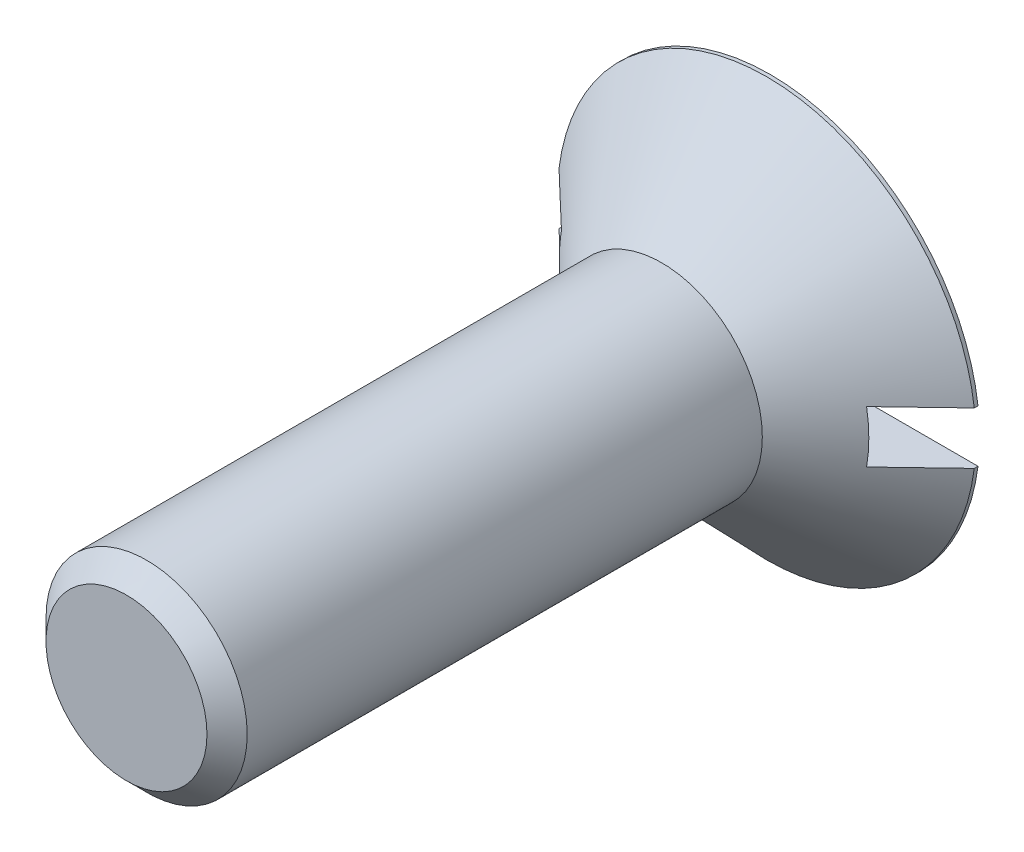
SolidWorks part; units mm, degrees
material "Acier allié"
ref_plane "Plan1" through (0, 0, 0) normal (0, 0, 1) x (1, 0, 0)
ref_plane "Plan2" through (0, 0, 0) normal (0, 1, 0) x (1, 0, 0)
ref_plane "Plan3" through (0, 0, 0) normal (1, 0, 0) x (0, 0, -1)
ref_axis "Z Axis" through (0, 0, -50) along (0, 0, 1)
sketch "Esquisse1" plane through (0, 0, 0) normal (0, 1, 0) x (1, 0, 0)
  line L0 (2.5, 0) -> (5.2, 2.6074)
  line L1 (0, 0) -> (2.5, 0)
  line L2 (0, 0) -> (0, 2.7)
  line L3 (0, 2.7) -> (5.2, 2.7)
  line L5 (5.2, 2.6074) -> (5.2, 2.7)
  line L6 (0, 0) -> (0, 2.7) construction
  dimension "D3" = 5.2
  dimension "D1" = 2.5
  dimension "D2" = 46
  dimension "D4" = 2.7
revolve "Base-Révolution" add sketch "Esquisse1" angle 360 about L6 reverse direction yes
sketch "Esquisse2" plane through (0, 0, -2.7) normal (0, 0, 1) x (1, 0, 0)
  line L1 (-5.2, 0.65) -> (5.2, 0.65)
  line L2 (-5.2, 0.65) -> (-5.2, -0.65)
  line L3 (-5.2, -0.65) -> (5.2, -0.65)
  line L4 (5.2, 0.65) -> (5.2, -0.65)
  circle A1 centre (0, 0) radius 5.2 construction
extrude "fente1" cut sketch "Esquisse2" along normal blind 1.4
sketch "Esquisse3" plane through (0, 0, 0) normal (0, 1, 0) x (1, 0, 0)
  line L1 (0, 0) -> (0, -13.3) construction
  line L2 (0, 0) -> (2.5, 0)
  line L3 (0, 0) -> (0, -13.3)
  line L4 (0, -13.3) -> (2.5, -13.3)
  line L6 (2.5, 0) -> (2.5, -13.3)
  dimension "D1" = 13.3
  dimension "D2" = 2.5
revolve "Boss.-Révol.1" add sketch "Esquisse3"
cosmetic thread "Représentation de filetage1" [suppressed]
chamfer "Chanfrein1" distance 0.5 angle 45 1 edges at (2.5, 0, 13.3)
sketch "Esquisse4" plane through (0, 0, 0) normal (0, 1, 0) x (1, 0, 0)
  line L0 (2.012, -13.3488) -> (2.012, -13.2512)
  line L2 (2.012, -13.2512) -> (2.5488, -12.9413)
  line L3 (2.012, -13.3488) -> (2.5488, -13.6587)
  line L4 (2.5488, -12.9413) -> (2.5488, -13.6587)
  line L6 (-2.5, -13.3) -> (2.5, -13.3) construction
  line L7 (2.5, -13.3) -> (2.5, 0) construction
  point P4 (2.5, -13.3)
  dimension "D2" = 0.0488
  dimension "D3" = 0.0488
  dimension "D4" = 0.5368
  dimension "D5" = 60
  dimension "D1" = 0.488
  dimension "D6" = 60
sketch "Esquisse5" plane through (0, 0, 13.3) normal (0, 0, 1) x (1, 0, 0)
  circle A0 centre (0, 0) radius 2.5 construction
  circle A1 centre (0, 0) radius 2.5
curve "Hélice1" pitch 0.8 height 13.3 turns 16.625
sweep "Enlèvement de matière-Balayage1" [suppressed] cut profiles "Esquisse4" path "Hélice1"
equation "\"D1@Chanfrein1\"=\"D2@Esquisse3\"*0.2"
equation "\"D3@Esquisse4\"=0.1*\"D1@Esquisse4\""
equation "\"D4@Esquisse4\"=1.1*\"D1@Esquisse4\""
equation "\"D2@Esquisse4\"=0.1*\"D1@Esquisse4\""
equation "\"D1@Esquisse4\"=0.61*\"D4@Hélice1\""
equation "\"D2@Esquisse3\"=\"D1@Esquisse1\""
equation "\"D1@Représentation de filetage1\"=\"D3@Hélice1\""
equation "\"D2@Représentation de filetage1\" = \"D2@Esquisse3\"*1.6"
